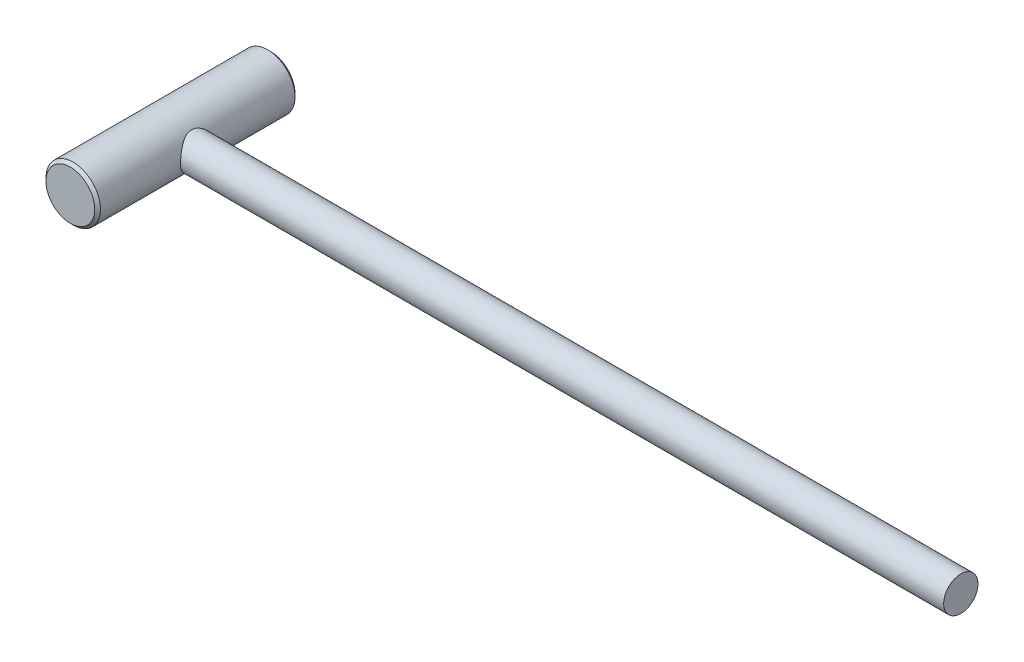
SolidWorks part; units mm, degrees
material "AISI 304 Stainless Steel"
ref_plane "Front Plane" through (0, 0, 0) normal (0, 0, 1) x (1, 0, 0)
ref_plane "Top Plane" through (0, 0, 0) normal (0, 1, 0) x (1, 0, 0)
ref_plane "Right Plane" through (0, 0, 0) normal (1, 0, 0) x (0, 0, -1)
ref_axis "Axis1" through (0, 0, -88.99) along (0, 0, 1)
ref_axis "Axis2" through (0, -55, 0) along (0, 1, 0)
ref_axis "Axis3" through (-88.99, 0, 0) along (1, 0, 0)
sketch "Sketch1" plane through (0, 0, 0) normal (0, 0, 1) x (1, 0, 0)
  circle A0 centre (0, 0) radius 4.7625
  dimension "D1" = 9.525
extrude "Boss-Extrude1" add sketch "Sketch1" along normal mid plane 35
ref_plane "Plane1" through (4.7625, 0, 0) normal (1, 0, 0) x (0, 0, -1)
hole_wizard "1/4-20 Tapped Hole1" positions "Sketch3" profile "Sketch2" tap size "1/4-20" standard "ANSI Inch"
sketch "Sketch3" plane through (4.7625, 0, 0) normal (1, 0, 0) x (0, 0, -1)
  point P0 (0, 0)
cosmetic thread "Hole Thread1" parameters "D1"=7, "D2"=6.35
sketch "Sketch2" plane through (4.7625, 0, 0) normal (0, 1, 0) x (0, 0, -1)
  line L0 (0, 0) -> (0, 9.5338)
  line L1 (0, 9.5338) -> (2.5527, 8)
  line L2 (2.5527, 8) -> (2.5527, 0)
  line L5 (2.5527, 0) -> (0, 0)
  line L10 (0, 9.5338) -> (-2.5527, 8) construction
  line L11 (0, -6.35) -> (0, 107.95) construction
  dimension "Tap Drill Dia." = 5.1054
  dimension "Tap Drill Depth" = 8
  dimension "Drill Angle" = 118
sketch "Sketch4" plane through (4.7625, 0, 0) normal (1, 0, 0) x (0, 0, -1)
  circle A0 centre (0, 0) radius 3
  dimension "D1" = 6
extrude "Boss-Extrude2" add sketch "Sketch4" along normal blind 133.35 and the other way blind 7 separate body
chamfer "Chamfer1" distance 0.5 angle 45 2 edges at (4.7625, 0, -17.5) (4.7625, 0, 17.5)
